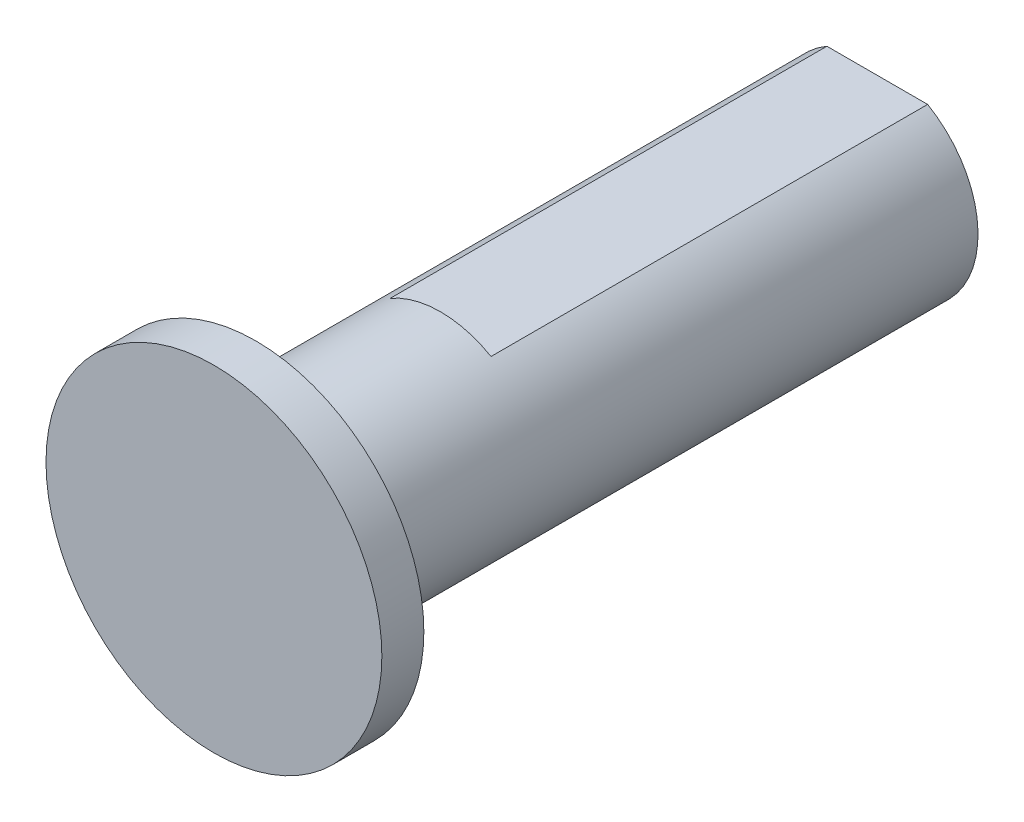
SolidWorks part; units mm, degrees
ref_plane "Front Plane" through (0, 0, 0) normal (0, 0, 1) x (1, 0, 0)
ref_plane "Top Plane" through (0, 0, 0) normal (0, 1, 0) x (1, 0, 0)
ref_plane "Right Plane" through (0, 0, 0) normal (1, 0, 0) x (0, 0, -1)
sketch "Sketch1" plane through (0, 0, 0) normal (0, 0, 1) x (1, 0, 0)
  line L0 (-3, 5.1962) -> (3, 5.1962)
  circle A0 centre (0, 0) radius 6
  dimension "D1" = 12
  dimension "D2" = 6
extrude "Boss-Extrude1" add sketch "Sketch1" along normal blind 37 contours A0
sketch "Sketch2" plane through (0, 0, 0) normal (0, 0, -1) x (-1, 0, 0)
  line L0 (-3, 5.1962) -> (3, 5.1962)
  circle A1 centre (0, 0) radius 6 construction
  circle A2 centre (0, 0) radius 6
  circle M3 centre (0, 0) radius 6
  dimension "D1" = 6
extrude "Cut-Extrude1" cut sketch "Sketch2" against normal blind 26 contours L0 M3 region at (0, 5.5196, 0)
sketch "Sketch3" plane through (0, 0, 37) normal (0, 0, 1) x (1, 0, 0)
  circle A0 centre (0, 0) radius 10
  dimension "D1" = 20
extrude "Boss-Extrude2" add sketch "Sketch3" along normal blind 2.5
